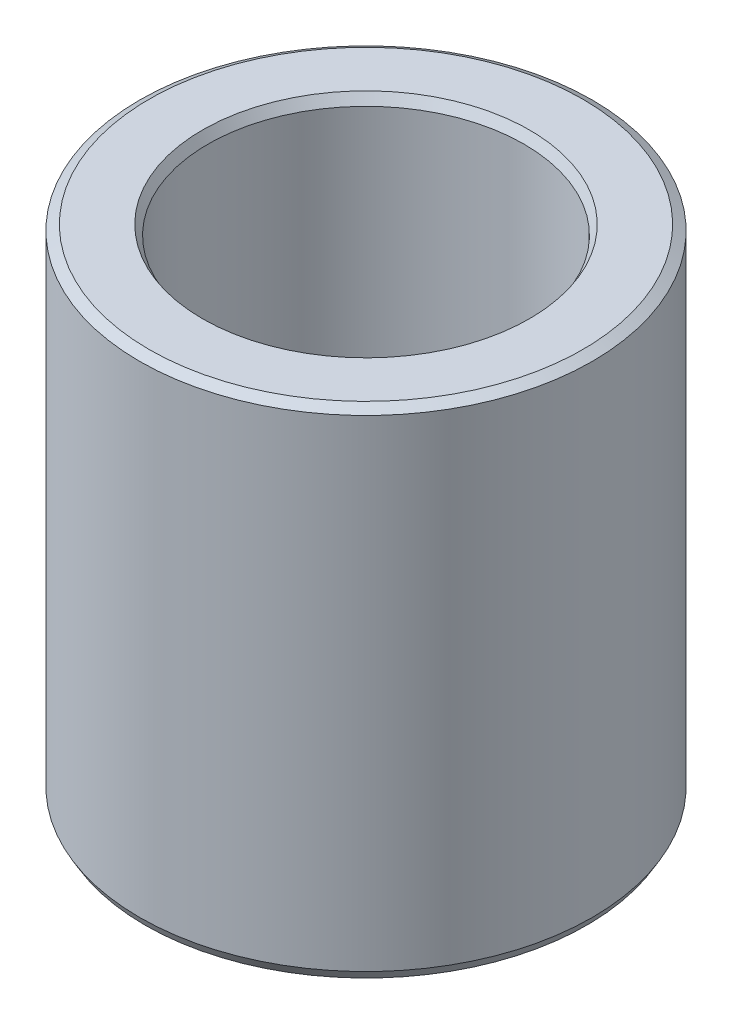
SolidWorks part; units mm, degrees
ref_plane "Front Plane" through (0, 0, 0) normal (0, 0, 1) x (1, 0, 0)
ref_plane "Top Plane" through (0, 0, 0) normal (0, 1, 0) x (1, 0, 0)
ref_plane "Right Plane" through (0, 0, 0) normal (1, 0, 0) x (0, 0, -1)
sketch "Sketch1" plane through (0, 0, 0) normal (0, 1, 0) x (1, 0, 0)
  circle A0 centre (0, 0) radius 35
  dimension "SLEEVE_OD" = 70
extrude "Boss-Extrude1" add sketch "Sketch1" along normal blind 76.7836
sketch "Sketch2" plane through (0, 0, 0) normal (0, 1, 0) x (1, 0, 0)
  circle A0 centre (0, 0) radius 24.4362
  dimension "BORE_D" = 48.8724
extrude "Cut-Extrude1" cut sketch "Sketch2" along normal through all
chamfer "Chamfer1" distance 0.8493 angle 60 4 edges at (0, 76.7836, 24.4362) (0, 0, 24.4362) (0, 0, 35) (0, 76.7836, 35) first distance on face at (0, 76.7836, 24.4362) first distance on face at (0, 0, 24.4362) first distance on face at (0, 76.7836, 35)
